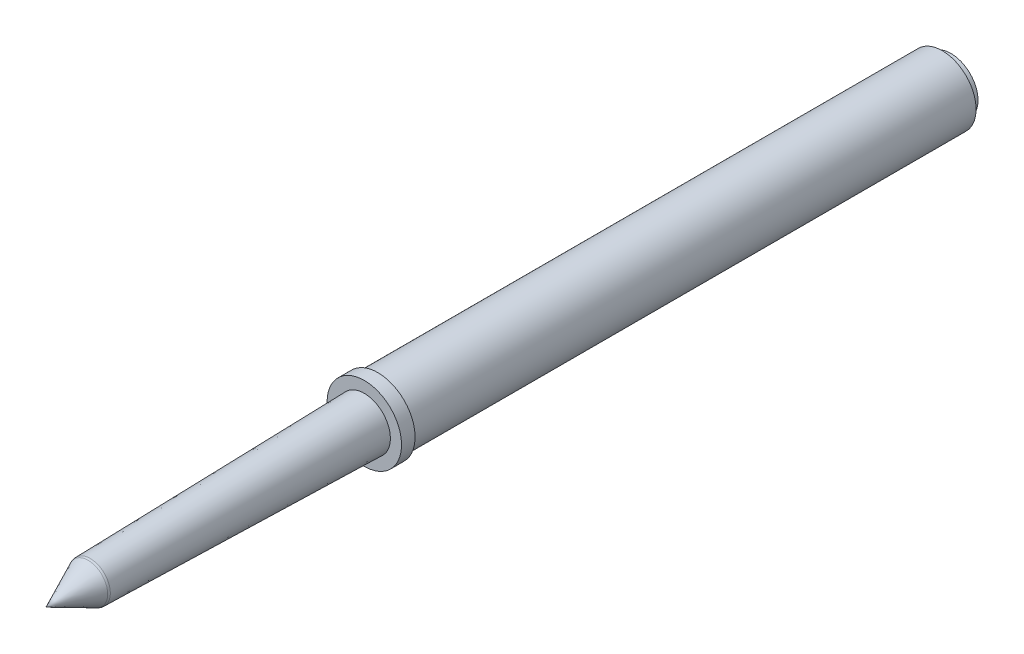
SolidWorks part; units mm, degrees
ref_plane "Front Plane" through (0, 0, 0) normal (0, 0, 1) x (1, 0, 0)
ref_plane "Top Plane" through (0, 0, 0) normal (0, 1, 0) x (1, 0, 0)
ref_plane "Right Plane" through (0, 0, 0) normal (1, 0, 0) x (0, 0, -1)
sketch "Sketch3" plane through (0, 0, 0) normal (1, 0, 0) x (0, 0, -1)
  line L0 (0, 0) -> (-259.5858, 0) construction
  line L4 (-203.0866, 0) -> (0, 0)
  line L6 (-201.8447, 4.6891) -> (-137.5866, 6.1099)
  line L7 (-137.5866, 6.1099) -> (-137.5866, 8.7312)
  line L8 (-137.5866, 8.7312) -> (-134.4116, 8.7312)
  line L11 (-2.0454, 7.9375) -> (-2.0454, 6.35)
  line L12 (-2.0454, 6.35) -> (0, 6.35)
  line L13 (0, 6.35) -> (0, 0)
  line L15 (-141.0866, 6.0325) -> (-141.0866, 0) construction
  line L16 (-137.5866, 6.1099) -> (-168.6233, 6.1099) construction
  line L22 (-203.0866, 3.4195) -> (-203.0866, 0) construction
  line L23 (-202.3495, 4.5723) -> (-212.2421, 0)
  line L24 (-212.2421, 0) -> (-203.0866, 0)
  line L30 (-134.4116, 8.7312) -> (-134.4116, 7.9375)
  line L32 (-134.4116, 7.9375) -> (-2.0454, 7.9375)
  arc A0 (-202.3495, 4.5723) -> (-201.8447, 4.6891) centre (-201.8166, 3.4195) cw
  point P3 (-141.0866, 6.0325)
  point P5 (-203.0866, 4.6617)
  point P12 (-137.5866, 7.4206)
  point P13 (-212.2421, 0)
  dimension "D2" = 65.5
  dimension "D9" = 1.27
  dimension "D3" = 17.4625
  dimension "D4" = 12.7
  dimension "D5" = 15.875
  dimension "D6" = 74.6554
  dimension "D7" = 3.175
  dimension "D8" = 24.806
  dimension "D10" = 3.5
  dimension "D11" = 12.065
  dimension "D13" = 1.267
revolve "Revolve2" add sketch "Sketch3" angle 360 about L0 region at (0, 3.6316, 94.9841)
ref_plane "Plane1" through (0, 7.9375, 0) normal (0, 1, 0) x (1, 0, 0)
sketch "Sketch4" plane through (0, 7.9375, 0) normal (0, 1, 0) x (1, 0, 0)
  line L0 (0, 0) -> (0, -62.8551) construction
  line L1 (2.3813, -80.3176) -> (-2.3812, -80.3176)
  line L2 (2.3813, -80.3176) -> (2.3813, -45.3926)
  line L3 (2.3813, -45.3926) -> (-2.3812, -45.3926)
  line L4 (-2.3812, -80.3176) -> (-2.3812, -45.3926)
  line L5 (2.3813, -80.3176) -> (-2.3812, -45.3926) construction
  line L6 (2.3813, -45.3926) -> (-2.3812, -80.3176) construction
  point P0 (0, -62.8551)
  dimension "D1" = 34.925
  dimension "D2" = 4.7625
extrude "Cut-Extrude1" [suppressed] cut sketch "Sketch4" against normal blind 2.3813
